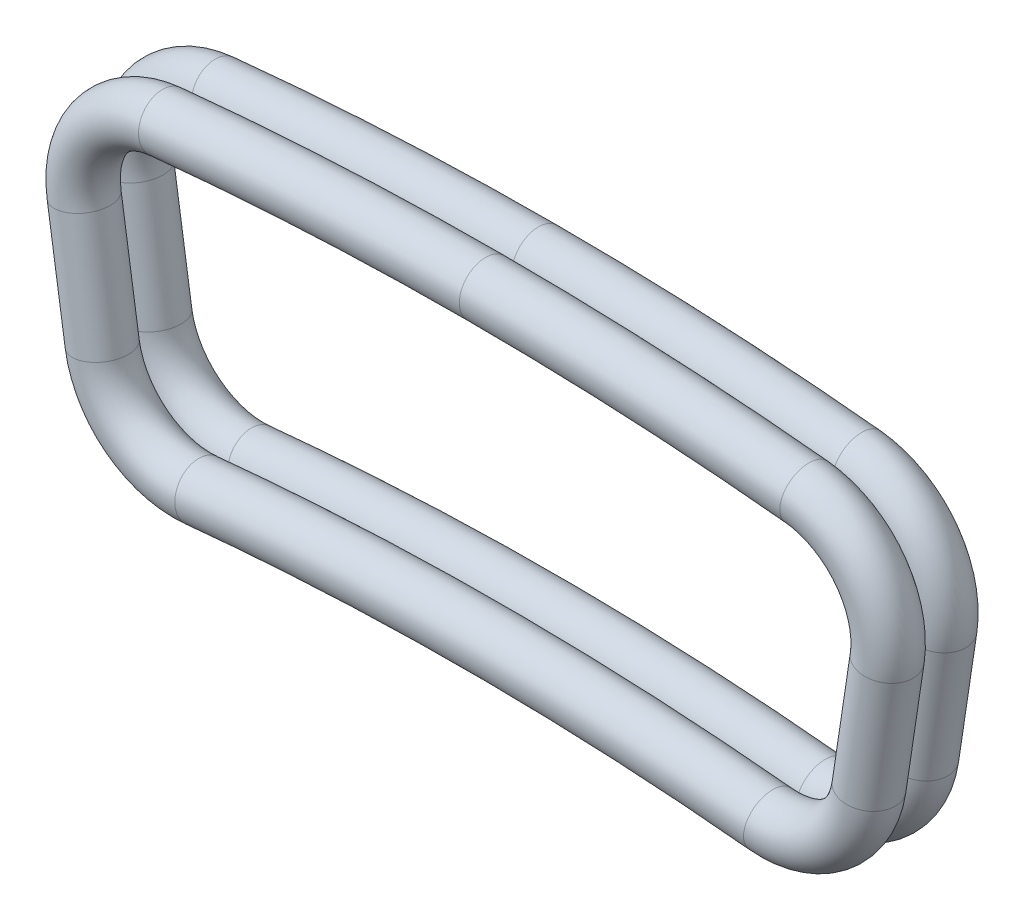
SolidWorks part; units mm, degrees
material "Copper"
ref_plane "Front Plane" through (0, 0, 0) normal (0, 0, 1) x (1, 0, 0)
ref_plane "Top Plane" through (0, 0, 0) normal (0, 1, 0) x (1, 0, 0)
ref_plane "Right Plane" through (0, 0, 0) normal (1, 0, 0) x (0, 0, -1)
sketch "Sketch1" plane through (0, 0, 0) normal (0, 0, 1) x (1, 0, 0)
  line L0 (11.8453, 90.7593) -> (12.404, 94.466)
  line L1 (-12.404, 94.466) -> (-11.8453, 90.7593)
  line L2 (11.0404, 90.8806) -> (11.5991, 94.5874)
  line L3 (-11.5991, 94.5874) -> (-11.0404, 90.8806)
  line L4 (11.0404, 90.8806) -> (11.5991, 94.5874) construction
  line L5 (-11.5991, 94.5874) -> (-11.0404, 90.8806) construction
  arc A0 (12.404, 94.466) -> (9.9053, 97.6851) centre (9.6214, 94.8854) ccw
  arc A1 (9.9053, 97.6851) -> (-9.9053, 97.6851) centre (0, 0) ccw
  arc A2 (-9.9053, 97.6851) -> (-12.404, 94.466) centre (-9.6214, 94.8854) ccw
  arc A3 (-11.8453, 90.7593) -> (-8.7844, 88.3785) centre (-9.0627, 91.1787) ccw
  arc A4 (8.7844, 88.3785) -> (-8.7844, 88.3785) centre (0, 0) ccw
  arc A5 (8.7844, 88.3785) -> (11.8453, 90.7593) centre (9.0627, 91.1787) ccw
  arc A6 (11.5991, 94.5874) -> (9.8232, 96.8752) centre (9.6214, 94.8854) ccw
  arc A7 (9.8232, 96.8752) -> (-9.8232, 96.8752) centre (0, 0) ccw
  arc A8 (-9.8232, 96.8752) -> (-11.5991, 94.5874) centre (-9.6214, 94.8854) ccw
  arc A9 (-11.0404, 90.8806) -> (-8.8649, 89.1885) centre (-9.0627, 91.1787) ccw
  arc A10 (8.8649, 89.1885) -> (-8.8649, 89.1885) centre (0, 0) ccw
  arc A11 (8.8649, 89.1885) -> (11.0404, 90.8806) centre (9.0627, 91.1787) ccw
  arc A12 (11.5991, 94.5874) -> (9.8232, 96.8752) centre (9.6214, 94.8854) ccw construction
  arc A13 (9.8232, 96.8752) -> (-9.8232, 96.8752) centre (0, 0) ccw construction
  arc A14 (-9.8232, 96.8752) -> (-11.5991, 94.5874) centre (-9.6214, 94.8854) ccw construction
  arc A15 (-11.0404, 90.8806) -> (-8.8649, 89.1885) centre (-9.0627, 91.1787) ccw construction
  arc A16 (8.8649, 89.1885) -> (-8.8649, 89.1885) centre (0, 0) ccw construction
  arc A17 (8.8649, 89.1885) -> (11.0404, 90.8806) centre (9.0627, 91.1787) ccw construction
  dimension "D1" = 0
  dimension "D2" = 0.814
ref_plane "Plane1" through (0, 0, -3.186) normal (0, 0, 1) x (1, 0, 0)
sketch "Sketch3" plane through (0, 0, -3.186) normal (0, 0, 1) x (1, 0, 0)
  line L0 (11.8453, 90.7593) -> (12.404, 94.466) construction
  line L1 (-12.404, 94.466) -> (-11.8453, 90.7593) construction
  line L2 (11.8453, 90.7593) -> (12.404, 94.466)
  line L3 (-12.404, 94.466) -> (-11.8453, 90.7593)
  arc A0 (12.404, 94.466) -> (9.9053, 97.6851) centre (9.6214, 94.8854) ccw construction
  arc A1 (8.7844, 88.3785) -> (11.8453, 90.7593) centre (9.0627, 91.1787) ccw construction
  arc A2 (8.7844, 88.3785) -> (-8.7844, 88.3785) centre (0, 0) ccw construction
  arc A3 (-11.8453, 90.7593) -> (-8.7844, 88.3785) centre (-9.0627, 91.1787) ccw construction
  arc A4 (-9.9053, 97.6851) -> (-12.404, 94.466) centre (-9.6214, 94.8854) ccw construction
  arc A5 (9.9053, 97.6851) -> (-9.9053, 97.6851) centre (0, 0) ccw construction
  arc A6 (12.404, 94.466) -> (9.9053, 97.6851) centre (9.6214, 94.8854) ccw
  arc A7 (8.7844, 88.3785) -> (11.8453, 90.7593) centre (9.0627, 91.1787) ccw
  arc A8 (8.7844, 88.3785) -> (-8.7844, 88.3785) centre (0, 0) ccw
  arc A9 (-11.8453, 90.7593) -> (-8.7844, 88.3785) centre (-9.0627, 91.1787) ccw
  arc A10 (-9.9053, 97.6851) -> (-12.404, 94.466) centre (-9.6214, 94.8854) ccw
  arc A11 (9.9053, 97.6851) -> (-9.9053, 97.6851) centre (0, 0) ccw
sketch "Sketch4" plane through (0, 0, 0) normal (1, 0, 0) x (0, 0, -1)
  circle A0 centre (3.186, 98.186) radius 0.814
  point P2 (-40.4162, 47.1736)
  point P3 (2, 103.785)
  dimension "D1" = 1.628
sweep "Sweep2" add profiles "Sketch4" path "Sketch3"
pattern_linear "LPattern1" count 2 spacing 1.628 along (0, 0, 1) of bodies 102
